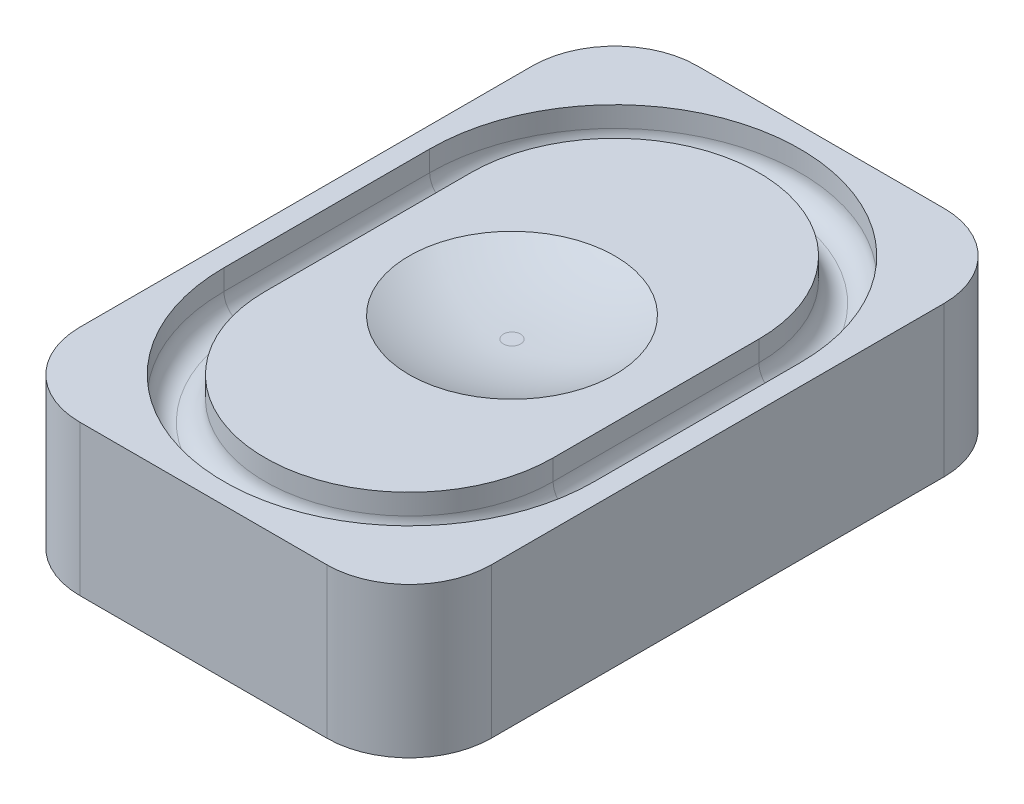
SolidWorks part; units mm, degrees
material "ABS"
ref_plane "Front Plane" through (0, 0, 0) normal (0, 0, 1) x (1, 0, 0)
ref_plane "Top Plane" through (0, 0, 0) normal (0, 1, 0) x (1, 0, 0)
ref_plane "Right Plane" through (0, 0, 0) normal (1, 0, 0) x (0, 0, -1)
sketch "Sketch1" plane through (0, 0, 0) normal (0, 1, 0) x (1, 0, 0)
  line L1 (-10, 15) -> (10, 15)
  line L2 (-10, 15) -> (-10, -15)
  line L3 (-10, -15) -> (10, -15)
  line L4 (10, 15) -> (10, -15)
  line L5 (0, -15) -> (0, 15) construction
  line L6 (-10, 0) -> (10, 0) construction
  point P0 (0, 0)
  dimension "D1" = 20
  dimension "D2" = 30
extrude "Boss-Extrude1" add sketch "Sketch1" along normal blind 7.3
fillet "Fillet1" radius 4 4 edges at (-10, 3.65, -15) (10, 3.65, -15) (-10, 3.65, 15) (10, 3.65, 15)
sketch "Sketch2" plane through (0, 7.3, 0) normal (0, 1, 0) x (1, 0, 0)
  line L0 (0, 5) -> (0, -5) construction
  line L1 (9, 5) -> (9, -5)
  line L2 (-9, 5) -> (-9, -5)
  line L3 (10, -11) -> (10, 11) construction
  line L4 (6, 15) -> (-6, 15) construction
  line L5 (7, 5) -> (7, -5)
  line L6 (-7, 5) -> (-7, -5)
  arc A0 (9, 5) -> (-9, 5) centre (0, 5) ccw
  arc A1 (-9, -5) -> (9, -5) centre (0, -5) ccw
  arc A2 (-7, -5) -> (7, -5) centre (0, -5) ccw
  arc A3 (7, 5) -> (-7, 5) centre (0, 5) ccw
  point P3 (0, 0)
  point P14 (0, 14)
  dimension "D1" = 1
  dimension "D2" = 1
  dimension "D3" = 2
extrude "Cut-Extrude1" cut sketch "Sketch2" against normal blind 2
fillet "Fillet2" radius 1 8 edges at (9, 5.3, 0) (0, 5.3, 14) (-9, 5.3, 0) (0, 5.3, -14) (0, 5.3, -12) (-7, 5.3, 0) (0, 5.3, 12) (7, 5.3, 0)
sketch "Sketch3" plane through (0, 7.3, 0) normal (0, 1, 0) x (1, 0, 0)
  circle A0 centre (0, 0) radius 5
  dimension "D1" = 10
extrude "Cut-Extrude2" cut sketch "Sketch3" against normal blind 1
fillet "Fillet3" radius 11 1 edges at (0, 6.3, 5)
